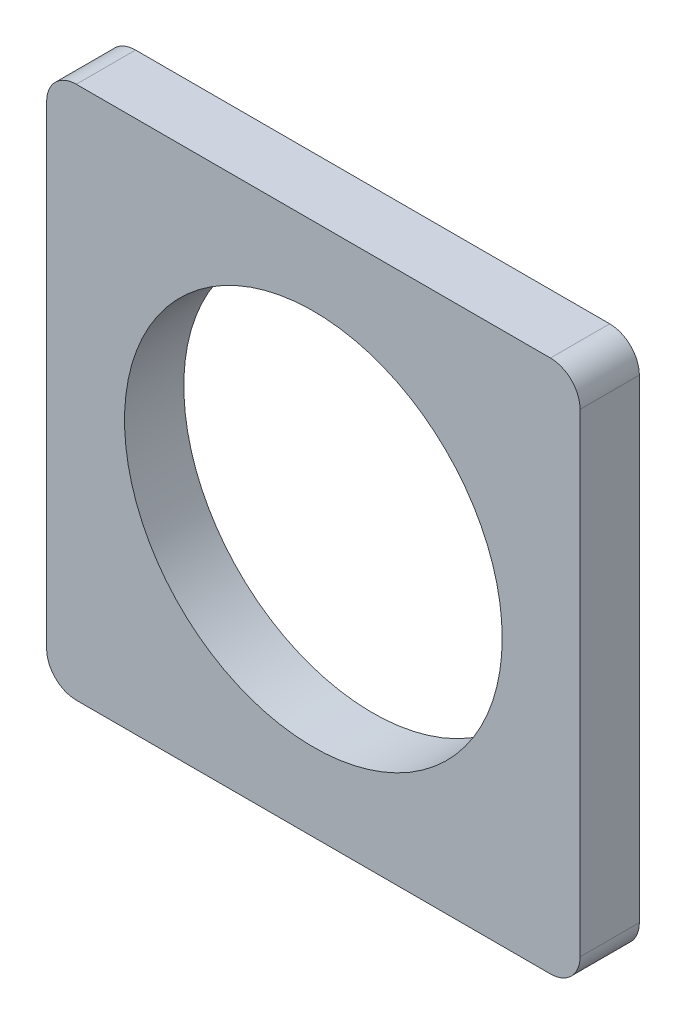
SolidWorks part; units mm, degrees
ref_plane "Front Plane" through (0, 0, 0) normal (0, 0, 1) x (1, 0, 0)
ref_plane "Top Plane" through (0, 0, 0) normal (0, 1, 0) x (1, 0, 0)
ref_plane "Right Plane" through (0, 0, 0) normal (1, 0, 0) x (0, 0, -1)
sketch "Sketch1" plane through (0, 0, 0) normal (0, 0, 1) x (1, 0, 0)
  line L1 (95.1641, -27.2927) -> (152.3141, -27.2927)
  line L2 (95.1641, -27.2927) -> (95.1641, 29.8573)
  line L3 (95.1641, 29.8573) -> (152.3141, 29.8573)
  line L4 (152.3141, -27.2927) -> (152.3141, 29.8573)
  line L5 (95.1641, -27.2927) -> (152.3141, 29.8573) construction
  line L6 (95.1641, 29.8573) -> (152.3141, -27.2927) construction
  circle A0 centre (123.7391, 1.2823) radius 20.2311 construction
  circle A1 centre (123.7391, 1.2823) radius 20.2311
  dimension "D1" = 28.575
  dimension "D2" = 28.575
extrude "Boss-Extrude1" add sketch "Sketch1" along normal blind 6.35
fillet "Fillet1" radius 3.175 4 edges at (95.1641, -27.2927, 3.175) (152.3141, -27.2927, 3.175) (95.1641, 29.8573, 3.175) (152.3141, 29.8573, 3.175)
